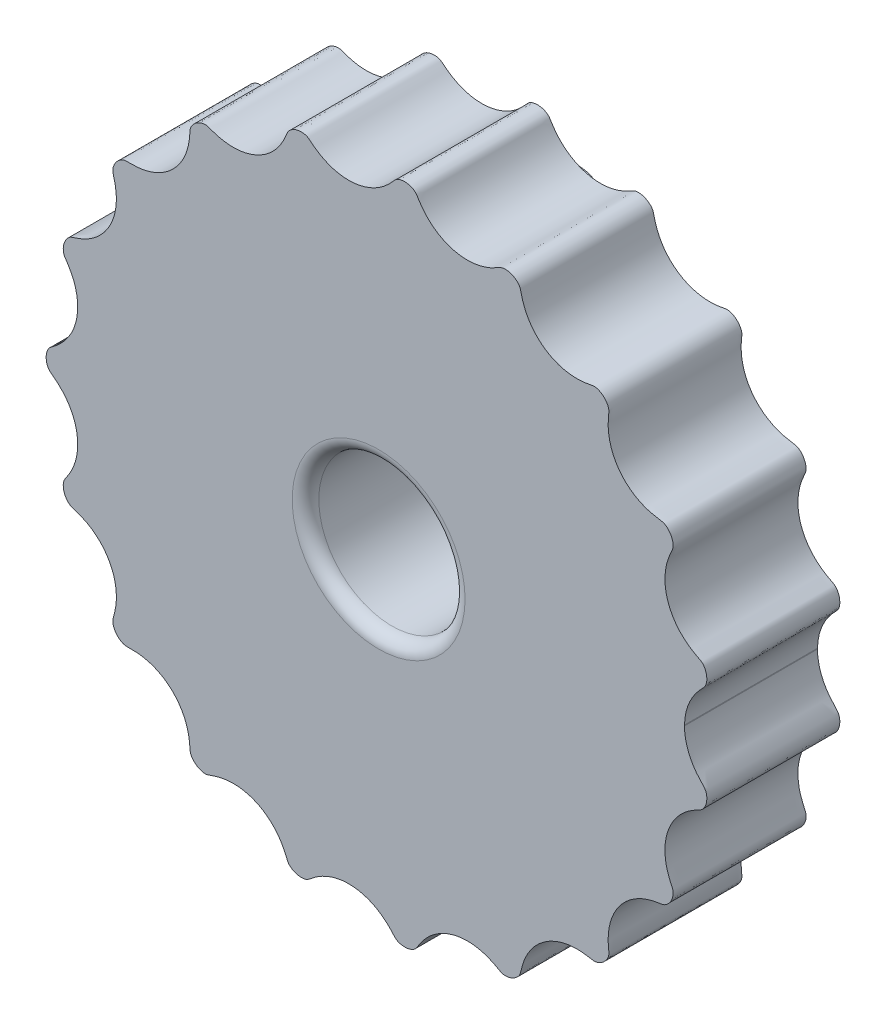
SolidWorks part; units mm, degrees
ref_plane "Ebene vorne" through (0, 0, 0) normal (0, 0, 1) x (1, 0, 0)
ref_plane "Ebene oben" through (0, 0, 0) normal (0, 1, 0) x (1, 0, 0)
ref_plane "Ebene rechts" through (0, 0, 0) normal (1, 0, 0) x (0, 0, -1)
sketch "Skizze1" plane through (0, 0, 0) normal (0, 0, 1) x (1, 0, 0)
  circle A0 centre (0, 0) radius 25
  dimension "D1" = 50
extrude "Aufsatz-Linear austragen1" add sketch "Skizze1" along normal blind 10 contours A0
sketch "Skizze3" plane through (0, 0, 10) normal (0, 0, 1) x (1, 0, 0)
  circle A0 centre (0, 25) radius 0.5
  circle A1 centre (0, 0) radius 25 construction
extrude "Schnitt-Linear austragen1" cut sketch "Skizze3" against normal up to next contours A0
pattern_circular "Kreismuster3" [suppressed] count 30 over 360 of bodies 102
sketch "Skizze9" plane through (0, 0, 10) normal (0, 0, 1) x (1, 0, 0)
  line L0 (23.0004, 0.0609) -> (23, 0)
  spline S0 degree 4 poles (21.8349, 10.4363) (21.7595, 10.2402) (21.6296, 9.8393) (21.51, 9.2154) (21.5169, 8.368) (21.6949, 7.529) (21.9996, 6.8362) (22.3616, 6.2918) (22.7278, 5.8789) (23.0126, 5.6175) (23.2743, 5.4145) (23.4929, 5.2661) (23.6607, 5.1622) (23.8217, 5.0701) (23.9556, 4.9977) (24.0711, 4.9376) (24.1728, 4.8842) (24.259, 4.8347) (24.3648, 4.7517) (24.4596, 4.6337) (24.5411, 4.4963) (24.6203, 4.3033) (24.6742, 4.0826) (24.6893, 3.8352) (24.654, 3.6047) (24.5939, 3.4337) (24.5231, 3.3149) (24.4482, 3.2274) (24.3391, 3.1139) (24.2149, 2.9815) (24.0838, 2.8346) (23.9185, 2.6346) (23.746, 2.4006) (23.5642, 2.1174) (23.3859, 1.7712) (23.2392, 1.419) (23.1381, 1.082) (23.0724, 0.8012) (23.0325, 0.5259) (23.0102, 0.3454) (22.9992, 0.0775) (22.999, -0.0665) (23.009, -0.3222) (23.0286, -0.4951) (23.0652, -0.7605) (23.1283, -1.0483) (23.2566, -1.484) (23.4559, -1.9318) (23.6809, -2.3132) (23.9099, -2.6224) (24.0743, -2.8241) (24.2067, -2.9723) (24.3336, -3.1084) (24.4467, -3.2256) (24.524, -3.3159) (24.583, -3.4156) (24.6246, -3.5208) (24.6638, -3.6686) (24.6852, -3.8609) (24.6735, -4.0869) (24.6205, -4.3068) (24.5464, -4.4848) (24.4695, -4.6144) (24.4037, -4.7024) (24.3311, -4.7784) (24.2516, -4.8395) (24.1377, -4.9039) (24.0001, -4.974) (23.846, -5.0565) (23.6352, -5.1762) (23.3933, -5.3292) (23.1212, -5.5276) (22.8316, -5.7799) (22.5655, -6.0569) (22.2617, -6.4361) (21.9548, -6.9332) (21.7249, -7.4811) (21.5829, -8.0653) (21.5273, -8.5636) (21.5216, -8.9708) (21.5541, -9.3694) (21.6218, -9.7561) (21.7087, -10.0818) (21.7995, -10.3483) (21.8842, -10.5632) (21.9558, -10.729) (22.0248, -10.8829) (22.0924, -11.0248) (22.1404, -11.1746) (22.1504, -11.3468) (22.1274, -11.5442) (22.061, -11.7619) (21.9505, -11.9788) (21.8083, -12.1674) (21.6614, -12.3022) (21.5247, -12.3914) (21.414, -12.4372) (21.3301, -12.4586) (21.2321, -12.4761) (21.1212, -12.4922) (20.9921, -12.5121) (20.8374, -12.539) (20.6763, -12.5709) (20.4655, -12.6198) (20.1205, -12.7175) (19.6539, -12.8972) (19.0899, -13.2109) (18.4957, -13.6939) (17.9798, -14.3033) (17.5818, -15.0184) (17.3599, -15.7125) (17.2758, -16.2728) (17.2579, -16.6757) (17.2603, -16.9123) (17.2683, -17.0871) (17.2802, -17.2498) (17.2921, -17.3816) (17.3037, -17.4944) (17.3123, -17.5952) (17.3148, -17.684) (17.3037, -17.7848) (17.2728, -17.8946) (17.2143, -18.0352) (17.1157, -18.1992) (16.9706, -18.3697) (16.7741, -18.5306) (16.5633, -18.6445) (16.3771, -18.7041) (16.228, -18.7183) (16.1024, -18.7064) (15.9827, -18.6847) (15.837, -18.6581) (15.664, -18.6292) (15.4825, -18.6042) (15.2505, -18.5802) (14.9676, -18.5655) (14.5429, -18.5729) (14.0693, -18.6361) (13.6043, -18.7559) (13.0666, -18.9667) (12.6278, -19.2052) (12.2149, -19.5036) (11.8389, -19.8586) (11.5583, -20.1838) (11.3157, -20.5303) (11.1115, -20.893) (10.9662, -21.2192) (10.865, -21.4994) (10.7941, -21.7329) (10.7511, -21.8937) (10.717, -22.0322) (10.6867, -22.159) (10.6596, -22.2741) (10.6135, -22.4098) (10.5273, -22.5357) (10.4274, -22.6442) (10.2911, -22.7583) (10.1265, -22.8625) (9.947, -22.94) (9.7581, -22.9885) (9.581, -23.009) (9.446, -23.0074) (9.3222, -22.9883) (9.215, -22.9494) (9.1367, -22.9105) (9.0374, -22.8556) (8.9163, -22.7867) (8.7704, -22.7082) (8.5994, -22.6214) (8.2969, -22.4821) (7.9364, -22.3488) (7.5146, -22.2402) (7.0313, -22.1759) (6.6328, -22.1607) (6.2298, -22.1836) (5.826, -22.2463) (5.4253, -22.3496) (5.032, -22.4941) (4.6565, -22.6767) (4.3023, -22.8948) (3.9755, -23.1429) (3.6777, -23.4168) (3.4441, -23.6748) (3.264, -23.904) (3.127, -24.0974) (3.026, -24.2496) (2.9434, -24.3794) (2.8771, -24.486) (2.8107, -24.5788) (2.7442, -24.6523) (2.6543, -24.7214) (2.5172, -24.8007) (2.3431, -24.8698) (2.129, -24.9172) (1.9104, -24.9257) (1.7254, -24.9049) (1.5597, -24.8634) (1.4272, -24.8123) (1.3018, -24.7374) (1.1919, -24.6254) (1.0929, -24.5126) (0.9862, -24.3949) (0.8714, -24.2728) (0.7167, -24.1173) (0.5166, -23.934) (0.1944, -23.6752) (-0.2816, -23.3734) (-0.8873, -23.1037) (-1.633, -22.9219) (-2.4119, -22.88) (-3.1838, -22.9833) (-3.829, -23.1953) (-4.2989, -23.431) (-4.6166, -23.6302) (-4.8236, -23.7746) (-4.9777, -23.8915) (-5.1193, -24.0037) (-5.2422, -24.1039) (-5.3368, -24.1704) (-5.4383, -24.2183) (-5.5428, -24.2496) (-5.6869, -24.2756) (-5.8715, -24.2822) (-6.0864, -24.2562) (-6.2931, -24.1927) (-6.4597, -24.1129) (-6.6006, -24.0204) (-6.7112, -23.9272) (-6.7966, -23.8241) (-6.8508, -23.7158) (-6.8984, -23.6058) (-6.9474, -23.4882) (-7.0086, -23.3469) (-7.0843, -23.183) (-7.1853, -22.982) (-7.3178, -22.7471) (-7.4915, -22.481) (-7.7159, -22.1922) (-7.9683, -21.919) (-8.2484, -21.6651) (-8.561, -21.4293) (-9, -21.1594) (-9.4852, -20.944) (-10.0058, -20.7949) (-10.5401, -20.7187) (-10.9664, -20.7017) (-11.386, -20.7263) (-11.7441, -20.7819) (-12.0407, -20.8508) (-12.2801, -20.9199) (-12.4645, -20.9804) (-12.619, -21.0347) (-12.7443, -21.0813) (-12.8432, -21.1127) (-12.9148, -21.1293) (-13.0155, -21.1409) (-13.1607, -21.1341) (-13.3458, -21.0947) (-13.5626, -21.0052) (-13.7727, -20.87) (-13.9463, -20.7079) (-14.067, -20.5439) (-14.1433, -20.3907) (-14.1772, -20.2506) (-14.1869, -20.1194) (-14.1984, -19.9464) (-14.2135, -19.7574) (-14.2357, -19.56) (-14.2744, -19.3096) (-14.3484, -18.9507) (-14.4988, -18.4602) (-14.7821, -17.8614) (-15.2347, -17.2299) (-15.8123, -16.6797) (-16.4915, -16.2457) (-17.1512, -15.9856) (-17.6884, -15.8653) (-18.0779, -15.8187) (-18.3444, -15.8008) (-18.5515, -15.7964) (-18.7472, -15.7971) (-18.9192, -15.8013) (-19.043, -15.798) (-19.1585, -15.7742) (-19.2639, -15.7342) (-19.3981, -15.6643) (-19.5524, -15.5524) (-19.7098, -15.3942) (-19.8355, -15.2104) (-19.9175, -15.0392) (-19.9694, -14.8748) (-19.9942, -14.7409) (-19.9941, -14.6091) (-19.9622, -14.4594) (-19.9209, -14.3132) (-19.8775, -14.147) (-19.8227, -13.9154) (-19.7703, -13.6388) (-19.7298, -13.3095) (-19.7155, -12.9316) (-19.7343, -12.5536) (-19.7865, -12.1771) (-19.8725, -11.8051) (-20.0235, -11.3478) (-20.2355, -10.9007) (-20.5061, -10.4779) (-20.8313, -10.0898) (-21.1296, -9.7984) (-21.4493, -9.5419) (-21.7859, -9.3207) (-22.0908, -9.1576) (-22.3541, -9.0395) (-22.5745, -8.9534) (-22.7489, -8.8919) (-22.9125, -8.8369) (-23.0664, -8.7897) (-23.2127, -8.7239) (-23.3488, -8.6133) (-23.48, -8.461) (-23.5959, -8.2631) (-23.6806, -8.0335) (-23.7223, -7.802) (-23.7216, -7.6015) (-23.6936, -7.4372) (-23.6459, -7.3113) (-23.587, -7.2131) (-23.5046, -7.0919) (-23.4135, -6.9559) (-23.317, -6.8055) (-23.1954, -6.601) (-23.0687, -6.3633) (-22.9383, -6.0757) (-22.7839, -5.6451) (-22.656, -5.1008) (-22.5992, -4.4221) (-22.6826, -3.6209) (-22.9272, -2.8308) (-23.2818, -2.1836) (-23.6363, -1.7308) (-23.9221, -1.4366) (-24.1011, -1.2722) (-24.239, -1.1546) (-24.372, -1.0482) (-24.4823, -0.963) (-24.578, -0.8915) (-24.662, -0.827) (-24.7323, -0.7672) (-24.8009, -0.6902) (-24.8613, -0.5932) (-24.925, -0.4573) (-24.9789, -0.2784) (-25.008, -0.0615) (-24.998, 0.1569) (-24.9616, 0.3399) (-24.9066, 0.5001) (-24.8504, 0.6156) (-24.7832, 0.7138) (-24.7061, 0.7903) (-24.6412, 0.8433) (-24.5549, 0.909) (-24.4487, 0.9887) (-24.3242, 1.0855) (-24.1833, 1.2011) (-24.0105, 1.3531) (-23.8111, 1.5469) (-23.5946, 1.788) (-23.3715, 2.0829) (-23.1734, 2.3976) (-23.0026, 2.7303) (-22.8251, 3.1685) (-22.6969, 3.6432) (-22.6277, 4.1442) (-22.6242, 4.6617) (-22.6664, 5.0951) (-22.7519, 5.5174) (-22.8777, 5.9244) (-23.0193, 6.2625) (-23.1587, 6.5356) (-23.2844, 6.7524) (-23.3883, 6.9169) (-23.4888, 7.0702) (-23.5875, 7.2108) (-23.6712, 7.3568) (-23.7142, 7.5309) (-23.7261, 7.7309) (-23.6995, 7.9535) (-23.6303, 8.1831) (-23.5263, 8.3908) (-23.4082, 8.549) (-23.2912, 8.6625) (-23.187, 8.7339) (-23.0968, 8.7758) (-22.9816, 8.8159) (-22.8484, 8.8583) (-22.6971, 8.9097) (-22.4871, 8.9859) (-22.2435, 9.0865) (-21.9662, 9.221) (-21.6596, 9.4005) (-21.366, 9.6063) (-21.0151, 9.8992) (-20.6164, 10.3191) (-20.2771, 10.8105) (-20.0144, 11.3636) (-19.8542, 11.8663) (-19.7673, 12.2789) (-19.7222, 12.6923) (-19.7169, 13.1024) (-19.7451, 13.4552) (-19.7902, 13.7494) (-19.8394, 13.9878) (-19.8839, 14.1718) (-19.9244, 14.3263) (-19.9596, 14.452) (-19.9815, 14.5509) (-19.9911, 14.6219) (-19.9935, 14.7217) (-19.9742, 14.8643) (-19.9195, 15.0445) (-19.8125, 15.2522) (-19.6794, 15.4254) (-19.5437, 15.5557) (-19.4017, 15.6607) (-19.2787, 15.7293) (-19.1504, 15.7794) (-19.0246, 15.7985) (-18.927, 15.8005) (-18.8133, 15.7991) (-18.6836, 15.7969) (-18.532, 15.7969) (-18.3106, 15.8023) (-18.0413, 15.8209) (-17.7248, 15.8628) (-17.3647, 15.941) (-16.9178, 16.0786) (-16.3974, 16.3085) (-15.8239, 16.6734) (-15.2485, 17.213) (-14.783, 17.8542) (-14.4878, 18.4827) (-14.3351, 18.9986) (-14.2627, 19.3751) (-14.2269, 19.6306) (-14.2075, 19.8274) (-14.1936, 20.0116) (-14.184, 20.1733) (-14.1697, 20.2905) (-14.1362, 20.4005) (-14.0873, 20.5015) (-14.0059, 20.6294) (-13.8804, 20.7742) (-13.7077, 20.9182) (-13.5127, 21.0276) (-13.335, 21.0939) (-13.1647, 21.1311) (-13.0232, 21.1444) (-12.8817, 21.1276) (-12.7469, 21.0817) (-12.6315, 21.0398) (-12.5001, 20.993) (-12.3519, 20.9431) (-12.1413, 20.8781) (-11.8655, 20.8075) (-11.5389, 20.7468) (-11.1616, 20.7097) (-10.7833, 20.7056) (-10.3038, 20.7432) (-9.7354, 20.8584) (-9.1818, 21.0633) (-8.6608, 21.3563) (-8.2599, 21.6542) (-7.9581, 21.9276) (-7.6875, 22.2243) (-7.4782, 22.5013) (-7.318, 22.7492) (-7.2006, 22.9556) (-7.1162, 23.1178) (-7.0401, 23.2775) (-6.9792, 23.4143) (-6.929, 23.5322) (-6.8829, 23.6417) (-6.8396, 23.7425) (-6.7732, 23.8583) (-6.6528, 23.9827) (-6.4911, 24.0996) (-6.2848, 24.1982) (-6.0489, 24.2635) (-5.8125, 24.2858) (-5.6133, 24.2679) (-5.4554, 24.2266) (-5.3475, 24.1752) (-5.2756, 24.1275) (-5.1963, 24.0667) (-5.1084, 23.9955) (-5.0052, 23.9133) (-4.8796, 23.817) (-4.7458, 23.7196) (-4.5657, 23.5973) (-4.2579, 23.4095) (-3.8065, 23.1883) (-3.1897, 22.9875) (-2.4297, 22.8812) (-1.6328, 22.9188) (-0.8411, 23.1135) (-0.1854, 23.421) (0.2799, 23.7378) (0.5861, 23.9964) (0.7572, 24.1576) (0.8795, 24.2813) (0.9904, 24.3996) (1.0788, 24.4971) (1.1534, 24.5815) (1.2215, 24.6556) (1.2849, 24.7171) (1.366, 24.7765) (1.4665, 24.8274) (1.6073, 24.879) (1.7912, 24.9173) (2.0109, 24.9275) (2.2284, 24.8982) (2.4076, 24.8457) (2.5635, 24.7759) (2.6787, 24.7064) (2.7776, 24.6216) (2.853, 24.522) (2.9089, 24.4353) (2.9741, 24.3312) (3.0513, 24.2111) (3.1673, 24.0378) (3.3314, 23.8136) (3.5412, 23.5623) (3.803, 23.2967) (4.0867, 23.0548) (4.3911, 22.8375) (4.7145, 22.6472) (5.1434, 22.4443) (5.6099, 22.2897) (6.1032, 22.1928) (6.6136, 22.1597) (7.04, 22.1755) (7.456, 22.233) (7.8578, 22.329) (8.1935, 22.443) (8.4659, 22.558) (8.6842, 22.6634) (8.8514, 22.7516) (9.0063, 22.8365) (9.1484, 22.9196) (9.3008, 22.9869) (9.4518, 23.0083) (9.5997, 23.0081) (9.7768, 22.9846) (9.9657, 22.9334) (10.1449, 22.8528) (10.3091, 22.7455) (10.4441, 22.6278) (10.5341, 22.5264) (10.6032, 22.4212) (10.6459, 22.3149) (10.6698, 22.2304) (10.6965, 22.1196) (10.7284, 21.9833) (10.7696, 21.8219) (10.8224, 21.6365) (10.926, 21.3181) (11.074, 20.9612) (11.2824, 20.576) (11.5658, 20.1761) (11.8273, 19.8724) (12.1194, 19.5924) (12.4404, 19.3397) (12.8767, 19.0608) (13.3474, 18.8414) (13.8414, 18.6865) (14.3466, 18.5977) (14.6978, 18.5693) (14.9983, 18.5678) (15.2424, 18.5806) (15.4319, 18.5983) (15.6163, 18.622) (15.7956, 18.651) (15.9629, 18.6804) (16.1188, 18.7114) (16.2634, 18.7186) (16.3919, 18.6957) (16.5434, 18.6484) (16.7128, 18.5663) (16.8932, 18.44) (17.0477, 18.2836) (17.1576, 18.1324) (17.2387, 17.9815) (17.2904, 17.8485) (17.3189, 17.7045) (17.3093, 17.5471) (17.2934, 17.3968) (17.2791, 17.2377) (17.2672, 17.07) (17.2581, 16.8499) (17.2594, 16.5774) (17.2886, 16.1632) (17.3914, 15.6061) (17.6071, 14.9758) (17.9828, 14.3047) (18.4824, 13.7066) (19.0811, 13.2137) (19.6713, 12.887) (20.16, 12.7034) (20.5195, 12.6059) (20.7644, 12.5521) (20.9536, 12.5182) (21.1309, 12.4903) (21.2868, 12.4679) (21.399, 12.4432) (21.5025, 12.4008) (21.5963, 12.345) (21.7134, 12.2561) (21.8437, 12.1238) (21.9702, 11.9469) (22.0634, 11.7504) (22.117, 11.5726) (22.1436, 11.4054) (22.149, 11.2598) (22.129, 11.1267) (22.0845, 11.0132) (22.035, 10.903) (21.9816, 10.7867) (21.919, 10.6454) (21.8499, 10.4782) (21.7706, 10.2666) (21.6878, 10.0086) (21.6103, 9.6986) (21.5509, 9.3355) (21.5224, 8.9626) (21.5272, 8.5827) (21.5787, 8.0866) (21.6972, 7.5846) (21.8865, 7.0905) (22.1457, 6.6199) (22.3909, 6.2662) (22.6666, 5.9438) (22.9679, 5.6541) (23.2503, 5.43) (23.5008, 5.2597) (23.7129, 5.1314) (23.8814, 5.0373) (24.0251, 4.9609) (24.1437, 4.9005) (24.2332, 4.8492) (24.2935, 4.8079) (24.37, 4.7415) (24.4633, 4.6297) (24.5599, 4.466) (24.6407, 4.2447) (24.683, 3.9972) (24.6804, 3.7586) (24.6403, 3.558) (24.5776, 3.3979) (24.4956, 3.2786) (24.4048, 3.1827) (24.2851, 3.0565) (24.1558, 2.9165) (24.0253, 2.7659) (23.8669, 2.5657) (23.6527, 2.2673) (23.442, 1.9019) (23.2546, 1.4742) (23.132, 1.0608) (23.0706, 0.7861) (23.0335, 0.5349) (23.0132, 0.3678) (23.0003, 0.1223) (22.9986, -0.0189) (23.0056, -0.2852) (23.0253, -0.4661) (23.0615, -0.7427) (23.1239, -1.029) (23.2494, -1.4644) (23.4447, -1.9094) (23.6681, -2.2941) (23.8991, -2.6086) (24.0657, -2.8141) (24.1984, -2.9632) (24.3246, -3.0987) (24.4356, -3.2143) (24.5132, -3.3018) (24.5877, -3.4196) (24.6374, -3.5547) (24.6701, -3.7073) (24.6838, -3.9154) (24.6644, -4.1417) (24.6, -4.381) (24.4916, -4.5912) (24.3759, -4.7394) (24.2736, -4.8247) (24.1898, -4.8749) (24.0901, -4.9279) (23.9765, -4.9865) (23.845, -5.0574) (23.6862, -5.1471) (23.5208, -5.2483) (23.3047, -5.3926) (23.0455, -5.59) (22.7627, -5.8442) (22.3976, -6.2458) (22.0314, -6.7792) (21.7172, -7.4627) (21.5252, -8.2962) (21.504, -9.1452) (21.6139, -9.7724) (21.7382, -10.176) (21.8113, -10.3736) knots 0 0 0 0 0 0.004237 0.008483 0.012729 0.016973 0.021413 0.023634 0.025855 0.02808 0.029193 0.030306 0.031182 0.032058 0.032934 0.033372 0.03381 0.034372 0.034934 0.036073 0.036831 0.037589 0.039124 0.04064 0.041779 0.042264 0.042749 0.043421 0.044093 0.045438 0.046411 0.047385 0.049332 0.051278 0.053223 0.055168 0.057112 0.0582 0.059287 0.060374 0.061462 0.062481 0.063501 0.064521 0.06554 0.067576 0.069612 0.073551 0.075471 0.07643 0.07739 0.078785 0.079482 0.08018 0.080676 0.081172 0.081811 0.082451 0.083753 0.085056 0.086348 0.086986 0.087623 0.08809 0.088558 0.089098 0.089639 0.090721 0.091672 0.092623 0.094526 0.09649 0.098454 0.100357 0.102259 0.106274 0.110193 0.112266 0.114339 0.116366 0.118392 0.120318 0.122244 0.123155 0.124065 0.124975 0.125886 0.126558 0.12723 0.128129 0.12933 0.130553 0.131784 0.13302 0.134061 0.134556 0.135052 0.135429 0.135805 0.136559 0.137312 0.138066 0.138968 0.13987 0.141675 0.145292 0.149024 0.152819 0.157032 0.161293 0.165414 0.167417 0.168419 0.16942 0.170182 0.170945 0.171707 0.172088 0.17247 0.172983 0.173496 0.174127 0.174758 0.176047 0.177335 0.178622 0.179842 0.180858 0.181239 0.181621 0.182383 0.183306 0.18423 0.185154 0.186077 0.188008 0.189939 0.193707 0.195683 0.19766 0.201566 0.203743 0.205919 0.208066 0.210213 0.212256 0.214298 0.215257 0.216216 0.217175 0.217654 0.218133 0.218845 0.219557 0.220527 0.221173 0.221818 0.22313 0.224442 0.22509 0.225738 0.226717 0.227156 0.227596 0.228035 0.228475 0.229441 0.230408 0.231375 0.232341 0.236155 0.238143 0.24013 0.242157 0.244184 0.24627 0.248355 0.250487 0.252618 0.254674 0.25673 0.258747 0.260763 0.261683 0.262604 0.263524 0.264444 0.264789 0.265133 0.265821 0.26644 0.267059 0.26832 0.269582 0.270836 0.271447 0.272058 0.273021 0.273691 0.274361 0.275205 0.27605 0.276894 0.277739 0.279628 0.281518 0.285219 0.28907 0.292926 0.296908 0.300855 0.304679 0.306545 0.307478 0.308411 0.309767 0.310445 0.311123 0.311607 0.31209 0.312702 0.313313 0.314555 0.3158 0.31704 0.317653 0.318265 0.319194 0.319946 0.320323 0.320699 0.321608 0.322518 0.323427 0.324337 0.326144 0.327952 0.329828 0.331704 0.333634 0.335564 0.337712 0.342077 0.344294 0.346435 0.348576 0.350665 0.352755 0.353733 0.35471 0.355688 0.356666 0.357036 0.357406 0.357777 0.358147 0.359078 0.360318 0.361577 0.362842 0.364095 0.365072 0.365667 0.366263 0.366989 0.367716 0.369169 0.370082 0.370996 0.372823 0.376553 0.380398 0.384283 0.388402 0.39254 0.396544 0.398494 0.399468 0.400443 0.401928 0.402671 0.403414 0.403914 0.404414 0.405044 0.405674 0.406958 0.408242 0.409517 0.410142 0.410767 0.411715 0.412247 0.41278 0.413844 0.414778 0.415711 0.417578 0.419518 0.421458 0.423328 0.425198 0.427172 0.429146 0.433023 0.435141 0.437259 0.439338 0.441417 0.443393 0.445369 0.446301 0.447232 0.448164 0.449096 0.449784 0.450473 0.451382 0.452594 0.453825 0.455064 0.456299 0.457303 0.457852 0.458401 0.459003 0.459604 0.460806 0.461705 0.462604 0.464401 0.466234 0.468066 0.471816 0.475642 0.479892 0.484207 0.488376 0.490424 0.491448 0.492472 0.493275 0.494078 0.494881 0.495283 0.495684 0.496212 0.496739 0.497357 0.497975 0.499232 0.500491 0.501743 0.502362 0.50298 0.503902 0.504323 0.504745 0.505167 0.505588 0.506507 0.507426 0.508345 0.509264 0.511146 0.513029 0.51487 0.51671 0.518635 0.520559 0.52439 0.526593 0.528795 0.530975 0.533155 0.535264 0.537372 0.538353 0.539334 0.540315 0.541296 0.542048 0.5428 0.543686 0.54487 0.546076 0.547289 0.548505 0.549524 0.55004 0.550557 0.551041 0.551525 0.552494 0.553378 0.554262 0.556029 0.557808 0.559586 0.561418 0.563249 0.567013 0.571226 0.573386 0.575547 0.57763 0.579713 0.581758 0.583803 0.584757 0.585711 0.586665 0.587619 0.587981 0.588342 0.588703 0.589064 0.589991 0.591226 0.592482 0.593745 0.594375 0.595005 0.596035 0.596581 0.597126 0.597563 0.597999 0.598872 0.599744 0.600617 0.602465 0.604312 0.606175 0.608037 0.611883 0.615748 0.619804 0.623847 0.62776 0.629667 0.63062 0.631574 0.63296 0.633653 0.634347 0.63484 0.635333 0.635965 0.636598 0.63789 0.639181 0.640471 0.641084 0.641696 0.642695 0.643315 0.643934 0.644554 0.645174 0.64613 0.647085 0.648997 0.65091 0.652822 0.654719 0.656616 0.660595 0.664476 0.666551 0.668626 0.67065 0.672674 0.674636 0.675617 0.676598 0.67746 0.678322 0.679184 0.679615 0.680046 0.680718 0.68139 0.682294 0.683501 0.68473 0.685967 0.68721 0.688256 0.688745 0.689234 0.689614 0.689994 0.690755 0.691516 0.692276 0.693184 0.694091 0.695906 0.699541 0.703294 0.707104 0.711296 0.715529 0.719623 0.721614 0.722609 0.723605 0.724363 0.72512 0.725878 0.726257 0.726636 0.727147 0.727657 0.728278 0.728898 0.730163 0.731429 0.732687 0.7333 0.733914 0.734868 0.735387 0.735906 0.736425 0.736945 0.737866 0.738787 0.740628 0.742544 0.74446 0.746298 0.748136 0.750076 0.752015 0.75585 0.758014 0.760177 0.762308 0.764439 0.766466 0.768494 0.769446 0.770399 0.771352 0.772304 0.773011 0.773717 0.774692 0.775341 0.77599 0.777308 0.778627 0.779278 0.77993 0.780912 0.781353 0.781795 0.782237 0.782678 0.78365 0.784622 0.785593 0.786565 0.790399 0.792398 0.794396 0.796432 0.798468 0.800544 0.802619 0.806855 0.808898 0.810941 0.812947 0.81395 0.814953 0.815868 0.816783 0.817698 0.818613 0.819297 0.819981 0.820603 0.821225 0.822492 0.82376 0.825019 0.825633 0.826247 0.827208 0.827886 0.828563 0.829411 0.830258 0.831106 0.831953 0.833852 0.83575 0.83947 0.843342 0.847212 0.851172 0.85509 0.858888 0.860742 0.861669 0.862595 0.863943 0.864616 0.86529 0.86577 0.866251 0.866866 0.86748 0.868728 0.86998 0.871226 0.871843 0.872459 0.87339 0.87415 0.87453 0.874909 0.875821 0.876733 0.877645 0.878557 0.880376 0.882194 0.884081 0.885968 0.887906 0.889845 0.894123 0.896327 0.898531 0.900659 0.902786 0.904866 0.906945 0.907918 0.90889 0.909862 0.910835 0.911203 0.911571 0.911939 0.912307 0.913243 0.914489 0.915755 0.917025 0.918283 0.919266 0.919863 0.920461 0.92119 0.921919 0.923377 0.924296 0.925215 0.927054 0.930802 0.932735 0.934668 0.935643 0.936618 0.937593 0.938568 0.939657 0.940745 0.941834 0.942922 0.944896 0.946869 0.950817 0.952789 0.953776 0.954762 0.956135 0.956821 0.957507 0.957996 0.958485 0.959623 0.960381 0.961139 0.962673 0.964189 0.965328 0.965881 0.966433 0.966863 0.967294 0.968154 0.969015 0.969875 0.970969 0.972064 0.974253 0.976438 0.978623 0.98299 0.987244 0.991499 0.995751 1 1 1 1 1 construction
  spline S1 degree 4 poles (23, 0) (23, -0.0443) (23.0016, -0.1335) (23.009, -0.3222) (23.0286, -0.4951) (23.0652, -0.7605) (23.1283, -1.0483) (23.2566, -1.484) (23.4559, -1.9318) (23.6809, -2.3132) (23.9099, -2.6224) (24.0743, -2.8241) (24.2067, -2.9723) (24.3336, -3.1084) (24.4467, -3.2256) (24.524, -3.3159) (24.583, -3.4156) (24.6246, -3.5208) (24.6638, -3.6686) (24.6852, -3.8609) (24.6735, -4.0869) (24.6205, -4.3068) (24.5464, -4.4848) (24.4695, -4.6144) (24.4037, -4.7024) (24.3311, -4.7784) (24.2516, -4.8395) (24.1377, -4.9039) (24.0001, -4.974) (23.846, -5.0565) (23.6352, -5.1762) (23.3933, -5.3292) (23.1212, -5.5276) (22.8316, -5.7799) (22.5655, -6.0569) (22.2617, -6.4361) (21.9548, -6.9332) (21.7249, -7.4811) (21.5829, -8.0653) (21.5273, -8.5636) (21.5216, -8.9708) (21.5541, -9.3694) (21.6218, -9.7561) (21.7087, -10.0818) (21.7995, -10.3483) (21.8842, -10.5632) (21.9558, -10.729) (22.0248, -10.8829) (22.0924, -11.0248) (22.1404, -11.1746) (22.1504, -11.3468) (22.1274, -11.5442) (22.061, -11.7619) (21.9505, -11.9788) (21.8083, -12.1674) (21.6614, -12.3022) (21.5247, -12.3914) (21.414, -12.4372) (21.3301, -12.4586) (21.2321, -12.4761) (21.1212, -12.4922) (20.9921, -12.5121) (20.8374, -12.539) (20.6763, -12.5709) (20.4655, -12.6198) (20.1205, -12.7175) (19.6539, -12.8972) (19.0899, -13.2109) (18.4957, -13.6939) (17.9798, -14.3033) (17.5818, -15.0184) (17.3599, -15.7125) (17.2758, -16.2728) (17.2579, -16.6757) (17.2603, -16.9123) (17.2683, -17.0871) (17.2802, -17.2498) (17.2921, -17.3816) (17.3037, -17.4944) (17.3123, -17.5952) (17.3148, -17.684) (17.3037, -17.7848) (17.2728, -17.8946) (17.2143, -18.0352) (17.1157, -18.1992) (16.9706, -18.3697) (16.7741, -18.5306) (16.5633, -18.6445) (16.3771, -18.7041) (16.228, -18.7183) (16.1024, -18.7064) (15.9827, -18.6847) (15.837, -18.6581) (15.664, -18.6292) (15.4825, -18.6042) (15.2505, -18.5802) (14.9676, -18.5655) (14.5429, -18.5729) (14.0693, -18.6361) (13.6043, -18.7559) (13.0666, -18.9667) (12.6278, -19.2052) (12.2149, -19.5036) (11.8389, -19.8586) (11.5583, -20.1838) (11.3157, -20.5303) (11.1115, -20.893) (10.9662, -21.2192) (10.865, -21.4994) (10.7941, -21.7329) (10.7511, -21.8937) (10.717, -22.0322) (10.6867, -22.159) (10.6596, -22.2741) (10.6135, -22.4098) (10.5273, -22.5357) (10.4274, -22.6442) (10.2911, -22.7583) (10.1265, -22.8625) (9.947, -22.94) (9.7581, -22.9885) (9.581, -23.009) (9.446, -23.0074) (9.3222, -22.9883) (9.215, -22.9494) (9.1367, -22.9105) (9.0374, -22.8556) (8.9163, -22.7867) (8.7704, -22.7082) (8.5994, -22.6214) (8.2969, -22.4821) (7.9364, -22.3488) (7.5146, -22.2402) (7.0313, -22.1759) (6.6328, -22.1607) (6.2298, -22.1836) (5.826, -22.2463) (5.4253, -22.3496) (5.032, -22.4941) (4.6565, -22.6767) (4.3023, -22.8948) (3.9755, -23.1429) (3.6777, -23.4168) (3.4441, -23.6748) (3.264, -23.904) (3.127, -24.0974) (3.026, -24.2496) (2.9434, -24.3794) (2.8771, -24.486) (2.8107, -24.5788) (2.7442, -24.6523) (2.6543, -24.7214) (2.5172, -24.8007) (2.3431, -24.8698) (2.129, -24.9172) (1.9104, -24.9257) (1.7254, -24.9049) (1.5597, -24.8634) (1.4272, -24.8123) (1.3018, -24.7374) (1.1919, -24.6254) (1.0929, -24.5126) (0.9862, -24.3949) (0.8714, -24.2728) (0.7167, -24.1173) (0.5166, -23.934) (0.1944, -23.6752) (-0.2816, -23.3734) (-0.8873, -23.1037) (-1.633, -22.9219) (-2.4119, -22.88) (-3.1838, -22.9833) (-3.829, -23.1953) (-4.2989, -23.431) (-4.6166, -23.6302) (-4.8236, -23.7746) (-4.9777, -23.8915) (-5.1193, -24.0037) (-5.2422, -24.1039) (-5.3368, -24.1704) (-5.4383, -24.2183) (-5.5428, -24.2496) (-5.6869, -24.2756) (-5.8715, -24.2822) (-6.0864, -24.2562) (-6.2931, -24.1927) (-6.4597, -24.1129) (-6.6006, -24.0204) (-6.7112, -23.9272) (-6.7966, -23.8241) (-6.8508, -23.7158) (-6.8984, -23.6058) (-6.9474, -23.4882) (-7.0086, -23.3469) (-7.0843, -23.183) (-7.1853, -22.982) (-7.3178, -22.7471) (-7.4915, -22.481) (-7.7159, -22.1922) (-7.9683, -21.919) (-8.2484, -21.6651) (-8.561, -21.4293) (-9, -21.1594) (-9.4852, -20.944) (-10.0058, -20.7949) (-10.5401, -20.7187) (-10.9664, -20.7017) (-11.386, -20.7263) (-11.7441, -20.7819) (-12.0407, -20.8508) (-12.2801, -20.9199) (-12.4645, -20.9804) (-12.619, -21.0347) (-12.7443, -21.0813) (-12.8432, -21.1127) (-12.9148, -21.1293) (-13.0155, -21.1409) (-13.1607, -21.1341) (-13.3458, -21.0947) (-13.5626, -21.0052) (-13.7727, -20.87) (-13.9463, -20.7079) (-14.067, -20.5439) (-14.1433, -20.3907) (-14.1772, -20.2506) (-14.1869, -20.1194) (-14.1984, -19.9464) (-14.2135, -19.7574) (-14.2357, -19.56) (-14.2744, -19.3096) (-14.3484, -18.9507) (-14.4988, -18.4602) (-14.7821, -17.8614) (-15.2347, -17.2299) (-15.8123, -16.6797) (-16.4915, -16.2457) (-17.1512, -15.9856) (-17.6884, -15.8653) (-18.0779, -15.8187) (-18.3444, -15.8008) (-18.5515, -15.7964) (-18.7472, -15.7971) (-18.9192, -15.8013) (-19.043, -15.798) (-19.1585, -15.7742) (-19.2639, -15.7342) (-19.3981, -15.6643) (-19.5524, -15.5524) (-19.7098, -15.3942) (-19.8355, -15.2104) (-19.9175, -15.0392) (-19.9694, -14.8748) (-19.9942, -14.7409) (-19.9941, -14.6091) (-19.9622, -14.4594) (-19.9209, -14.3132) (-19.8775, -14.147) (-19.8227, -13.9154) (-19.7703, -13.6388) (-19.7298, -13.3095) (-19.7155, -12.9316) (-19.7343, -12.5536) (-19.7865, -12.1771) (-19.8725, -11.8051) (-20.0235, -11.3478) (-20.2355, -10.9007) (-20.5061, -10.4779) (-20.8313, -10.0898) (-21.1296, -9.7984) (-21.4493, -9.5419) (-21.7859, -9.3207) (-22.0908, -9.1576) (-22.3541, -9.0395) (-22.5745, -8.9534) (-22.7489, -8.8919) (-22.9125, -8.8369) (-23.0664, -8.7897) (-23.2127, -8.7239) (-23.3488, -8.6133) (-23.48, -8.461) (-23.5959, -8.2631) (-23.6806, -8.0335) (-23.7223, -7.802) (-23.7216, -7.6015) (-23.6936, -7.4372) (-23.6459, -7.3113) (-23.587, -7.2131) (-23.5046, -7.0919) (-23.4135, -6.9559) (-23.317, -6.8055) (-23.1954, -6.601) (-23.0687, -6.3633) (-22.9383, -6.0757) (-22.7839, -5.6451) (-22.656, -5.1008) (-22.5992, -4.4221) (-22.6826, -3.6209) (-22.9272, -2.8308) (-23.2818, -2.1836) (-23.6363, -1.7308) (-23.9221, -1.4366) (-24.1011, -1.2722) (-24.239, -1.1546) (-24.372, -1.0482) (-24.4823, -0.963) (-24.578, -0.8915) (-24.662, -0.827) (-24.7323, -0.7672) (-24.8009, -0.6902) (-24.8613, -0.5932) (-24.925, -0.4573) (-24.9789, -0.2784) (-25.008, -0.0615) (-24.998, 0.1569) (-24.9616, 0.3399) (-24.9066, 0.5001) (-24.8504, 0.6156) (-24.7832, 0.7138) (-24.7061, 0.7903) (-24.6412, 0.8433) (-24.5549, 0.909) (-24.4487, 0.9887) (-24.3242, 1.0855) (-24.1833, 1.2011) (-24.0105, 1.3531) (-23.8111, 1.5469) (-23.5946, 1.788) (-23.3715, 2.0829) (-23.1734, 2.3976) (-23.0026, 2.7303) (-22.8251, 3.1685) (-22.6969, 3.6432) (-22.6277, 4.1442) (-22.6242, 4.6617) (-22.6664, 5.0951) (-22.7519, 5.5174) (-22.8777, 5.9244) (-23.0193, 6.2625) (-23.1587, 6.5356) (-23.2844, 6.7524) (-23.3883, 6.9169) (-23.4888, 7.0702) (-23.5875, 7.2108) (-23.6712, 7.3568) (-23.7142, 7.5309) (-23.7261, 7.7309) (-23.6995, 7.9535) (-23.6303, 8.1831) (-23.5263, 8.3908) (-23.4082, 8.549) (-23.2912, 8.6625) (-23.187, 8.7339) (-23.0968, 8.7758) (-22.9816, 8.8159) (-22.8484, 8.8583) (-22.6971, 8.9097) (-22.4871, 8.9859) (-22.2435, 9.0865) (-21.9662, 9.221) (-21.6596, 9.4005) (-21.366, 9.6063) (-21.0151, 9.8992) (-20.6164, 10.3191) (-20.2771, 10.8105) (-20.0144, 11.3636) (-19.8542, 11.8663) (-19.7673, 12.2789) (-19.7222, 12.6923) (-19.7169, 13.1024) (-19.7451, 13.4552) (-19.7902, 13.7494) (-19.8394, 13.9878) (-19.8839, 14.1718) (-19.9244, 14.3263) (-19.9596, 14.452) (-19.9815, 14.5509) (-19.9911, 14.6219) (-19.9935, 14.7217) (-19.9742, 14.8643) (-19.9195, 15.0445) (-19.8125, 15.2522) (-19.6794, 15.4254) (-19.5437, 15.5557) (-19.4017, 15.6607) (-19.2787, 15.7293) (-19.1504, 15.7794) (-19.0246, 15.7985) (-18.927, 15.8005) (-18.8133, 15.7991) (-18.6836, 15.7969) (-18.532, 15.7969) (-18.3106, 15.8023) (-18.0413, 15.8209) (-17.7248, 15.8628) (-17.3647, 15.941) (-16.9178, 16.0786) (-16.3974, 16.3085) (-15.8239, 16.6734) (-15.2485, 17.213) (-14.783, 17.8542) (-14.4878, 18.4827) (-14.3351, 18.9986) (-14.2627, 19.3751) (-14.2269, 19.6306) (-14.2075, 19.8274) (-14.1936, 20.0116) (-14.184, 20.1733) (-14.1697, 20.2905) (-14.1362, 20.4005) (-14.0873, 20.5015) (-14.0059, 20.6294) (-13.8804, 20.7742) (-13.7077, 20.9182) (-13.5127, 21.0276) (-13.335, 21.0939) (-13.1647, 21.1311) (-13.0232, 21.1444) (-12.8817, 21.1276) (-12.7469, 21.0817) (-12.6315, 21.0398) (-12.5001, 20.993) (-12.3519, 20.9431) (-12.1413, 20.8781) (-11.8655, 20.8075) (-11.5389, 20.7468) (-11.1616, 20.7097) (-10.7833, 20.7056) (-10.3038, 20.7432) (-9.7354, 20.8584) (-9.1818, 21.0633) (-8.6608, 21.3563) (-8.2599, 21.6542) (-7.9581, 21.9276) (-7.6875, 22.2243) (-7.4782, 22.5013) (-7.318, 22.7492) (-7.2006, 22.9556) (-7.1162, 23.1178) (-7.0401, 23.2775) (-6.9792, 23.4143) (-6.929, 23.5322) (-6.8829, 23.6417) (-6.8396, 23.7425) (-6.7732, 23.8583) (-6.6528, 23.9827) (-6.4911, 24.0996) (-6.2848, 24.1982) (-6.0489, 24.2635) (-5.8125, 24.2858) (-5.6133, 24.2679) (-5.4554, 24.2266) (-5.3475, 24.1752) (-5.2756, 24.1275) (-5.1963, 24.0667) (-5.1084, 23.9955) (-5.0052, 23.9133) (-4.8796, 23.817) (-4.7458, 23.7196) (-4.5657, 23.5973) (-4.2579, 23.4095) (-3.8065, 23.1883) (-3.1897, 22.9875) (-2.4297, 22.8812) (-1.6328, 22.9188) (-0.8411, 23.1135) (-0.1854, 23.421) (0.2799, 23.7378) (0.5861, 23.9964) (0.7572, 24.1576) (0.8795, 24.2813) (0.9904, 24.3996) (1.0788, 24.4971) (1.1534, 24.5815) (1.2215, 24.6556) (1.2849, 24.7171) (1.366, 24.7765) (1.4665, 24.8274) (1.6073, 24.879) (1.7912, 24.9173) (2.0109, 24.9275) (2.2284, 24.8982) (2.4076, 24.8457) (2.5635, 24.7759) (2.6787, 24.7064) (2.7776, 24.6216) (2.853, 24.522) (2.9089, 24.4353) (2.9741, 24.3312) (3.0513, 24.2111) (3.1673, 24.0378) (3.3314, 23.8136) (3.5412, 23.5623) (3.803, 23.2967) (4.0867, 23.0548) (4.3911, 22.8375) (4.7145, 22.6472) (5.1434, 22.4443) (5.6099, 22.2897) (6.1032, 22.1928) (6.6136, 22.1597) (7.04, 22.1755) (7.456, 22.233) (7.8578, 22.329) (8.1935, 22.443) (8.4659, 22.558) (8.6842, 22.6634) (8.8514, 22.7516) (9.0063, 22.8365) (9.1484, 22.9196) (9.3008, 22.9869) (9.4518, 23.0083) (9.5997, 23.0081) (9.7768, 22.9846) (9.9657, 22.9334) (10.1449, 22.8528) (10.3091, 22.7455) (10.4441, 22.6278) (10.5341, 22.5264) (10.6032, 22.4212) (10.6459, 22.3149) (10.6698, 22.2304) (10.6965, 22.1196) (10.7284, 21.9833) (10.7696, 21.8219) (10.8224, 21.6365) (10.926, 21.3181) (11.074, 20.9612) (11.2824, 20.576) (11.5658, 20.1761) (11.8273, 19.8724) (12.1194, 19.5924) (12.4404, 19.3397) (12.8767, 19.0608) (13.3474, 18.8414) (13.8414, 18.6865) (14.3466, 18.5977) (14.6978, 18.5693) (14.9983, 18.5678) (15.2424, 18.5806) (15.4319, 18.5983) (15.6163, 18.622) (15.7956, 18.651) (15.9629, 18.6804) (16.1188, 18.7114) (16.2634, 18.7186) (16.3919, 18.6957) (16.5434, 18.6484) (16.7128, 18.5663) (16.8932, 18.44) (17.0477, 18.2836) (17.1576, 18.1324) (17.2387, 17.9815) (17.2904, 17.8485) (17.3189, 17.7045) (17.3093, 17.5471) (17.2934, 17.3968) (17.2791, 17.2377) (17.2672, 17.07) (17.2581, 16.8499) (17.2594, 16.5774) (17.2886, 16.1632) (17.3914, 15.6061) (17.6071, 14.9758) (17.9828, 14.3047) (18.4824, 13.7066) (19.0811, 13.2137) (19.6713, 12.887) (20.16, 12.7034) (20.5195, 12.6059) (20.7644, 12.5521) (20.9536, 12.5182) (21.1309, 12.4903) (21.2868, 12.4679) (21.399, 12.4432) (21.5025, 12.4008) (21.5963, 12.345) (21.7134, 12.2561) (21.8437, 12.1238) (21.9702, 11.9469) (22.0634, 11.7504) (22.117, 11.5726) (22.1436, 11.4054) (22.149, 11.2598) (22.129, 11.1267) (22.0845, 11.0132) (22.035, 10.903) (21.9816, 10.7867) (21.919, 10.6454) (21.8499, 10.4782) (21.7706, 10.2666) (21.6878, 10.0086) (21.6103, 9.6986) (21.5509, 9.3355) (21.5224, 8.9626) (21.5272, 8.5827) (21.5787, 8.0866) (21.6972, 7.5846) (21.8865, 7.0905) (22.1457, 6.6199) (22.3909, 6.2662) (22.6666, 5.9438) (22.9679, 5.6541) (23.2503, 5.43) (23.5008, 5.2597) (23.7129, 5.1314) (23.8814, 5.0373) (24.0251, 4.9609) (24.1437, 4.9005) (24.2332, 4.8492) (24.2935, 4.8079) (24.37, 4.7415) (24.4633, 4.6297) (24.5599, 4.466) (24.6407, 4.2447) (24.683, 3.9972) (24.6804, 3.7586) (24.6403, 3.558) (24.5776, 3.3979) (24.4956, 3.2786) (24.4048, 3.1827) (24.2851, 3.0565) (24.1558, 2.9165) (24.0253, 2.7659) (23.8669, 2.5657) (23.6527, 2.2673) (23.442, 1.9019) (23.2546, 1.4742) (23.132, 1.0608) (23.0706, 0.7861) (23.0335, 0.5349) (23.0132, 0.3678) (23.0038, 0.1889) (23.0011, 0.1033) (23.0004, 0.0609) knots 0.061462 0.061462 0.061462 0.061462 0.061462 0.062481 0.063501 0.064521 0.06554 0.067576 0.069612 0.073551 0.075471 0.07643 0.07739 0.078785 0.079482 0.08018 0.080676 0.081172 0.081811 0.082451 0.083753 0.085056 0.086348 0.086986 0.087623 0.08809 0.088558 0.089098 0.089639 0.090721 0.091672 0.092623 0.094526 0.09649 0.098454 0.100357 0.102259 0.106274 0.110193 0.112266 0.114339 0.116366 0.118392 0.120318 0.122244 0.123155 0.124065 0.124975 0.125886 0.126558 0.12723 0.128129 0.12933 0.130553 0.131784 0.13302 0.134061 0.134556 0.135052 0.135429 0.135805 0.136559 0.137312 0.138066 0.138968 0.13987 0.141675 0.145292 0.149024 0.152819 0.157032 0.161293 0.165414 0.167417 0.168419 0.16942 0.170182 0.170945 0.171707 0.172088 0.17247 0.172983 0.173496 0.174127 0.174758 0.176047 0.177335 0.178622 0.179842 0.180858 0.181239 0.181621 0.182383 0.183306 0.18423 0.185154 0.186077 0.188008 0.189939 0.193707 0.195683 0.19766 0.201566 0.203743 0.205919 0.208066 0.210213 0.212256 0.214298 0.215257 0.216216 0.217175 0.217654 0.218133 0.218845 0.219557 0.220527 0.221173 0.221818 0.22313 0.224442 0.22509 0.225738 0.226717 0.227156 0.227596 0.228035 0.228475 0.229441 0.230408 0.231375 0.232341 0.236155 0.238143 0.24013 0.242157 0.244184 0.24627 0.248355 0.250487 0.252618 0.254674 0.25673 0.258747 0.260763 0.261683 0.262604 0.263524 0.264444 0.264789 0.265133 0.265821 0.26644 0.267059 0.26832 0.269582 0.270836 0.271447 0.272058 0.273021 0.273691 0.274361 0.275205 0.27605 0.276894 0.277739 0.279628 0.281518 0.285219 0.28907 0.292926 0.296908 0.300855 0.304679 0.306545 0.307478 0.308411 0.309767 0.310445 0.311123 0.311607 0.31209 0.312702 0.313313 0.314555 0.3158 0.31704 0.317653 0.318265 0.319194 0.319946 0.320323 0.320699 0.321608 0.322518 0.323427 0.324337 0.326144 0.327952 0.329828 0.331704 0.333634 0.335564 0.337712 0.342077 0.344294 0.346435 0.348576 0.350665 0.352755 0.353733 0.35471 0.355688 0.356666 0.357036 0.357406 0.357777 0.358147 0.359078 0.360318 0.361577 0.362842 0.364095 0.365072 0.365667 0.366263 0.366989 0.367716 0.369169 0.370082 0.370996 0.372823 0.376553 0.380398 0.384283 0.388402 0.39254 0.396544 0.398494 0.399468 0.400443 0.401928 0.402671 0.403414 0.403914 0.404414 0.405044 0.405674 0.406958 0.408242 0.409517 0.410142 0.410767 0.411715 0.412247 0.41278 0.413844 0.414778 0.415711 0.417578 0.419518 0.421458 0.423328 0.425198 0.427172 0.429146 0.433023 0.435141 0.437259 0.439338 0.441417 0.443393 0.445369 0.446301 0.447232 0.448164 0.449096 0.449784 0.450473 0.451382 0.452594 0.453825 0.455064 0.456299 0.457303 0.457852 0.458401 0.459003 0.459604 0.460806 0.461705 0.462604 0.464401 0.466234 0.468066 0.471816 0.475642 0.479892 0.484207 0.488376 0.490424 0.491448 0.492472 0.493275 0.494078 0.494881 0.495283 0.495684 0.496212 0.496739 0.497357 0.497975 0.499232 0.500491 0.501743 0.502362 0.50298 0.503902 0.504323 0.504745 0.505167 0.505588 0.506507 0.507426 0.508345 0.509264 0.511146 0.513029 0.51487 0.51671 0.518635 0.520559 0.52439 0.526593 0.528795 0.530975 0.533155 0.535264 0.537372 0.538353 0.539334 0.540315 0.541296 0.542048 0.5428 0.543686 0.54487 0.546076 0.547289 0.548505 0.549524 0.55004 0.550557 0.551041 0.551525 0.552494 0.553378 0.554262 0.556029 0.557808 0.559586 0.561418 0.563249 0.567013 0.571226 0.573386 0.575547 0.57763 0.579713 0.581758 0.583803 0.584757 0.585711 0.586665 0.587619 0.587981 0.588342 0.588703 0.589064 0.589991 0.591226 0.592482 0.593745 0.594375 0.595005 0.596035 0.596581 0.597126 0.597563 0.597999 0.598872 0.599744 0.600617 0.602465 0.604312 0.606175 0.608037 0.611883 0.615748 0.619804 0.623847 0.62776 0.629667 0.63062 0.631574 0.63296 0.633653 0.634347 0.63484 0.635333 0.635965 0.636598 0.63789 0.639181 0.640471 0.641084 0.641696 0.642695 0.643315 0.643934 0.644554 0.645174 0.64613 0.647085 0.648997 0.65091 0.652822 0.654719 0.656616 0.660595 0.664476 0.666551 0.668626 0.67065 0.672674 0.674636 0.675617 0.676598 0.67746 0.678322 0.679184 0.679615 0.680046 0.680718 0.68139 0.682294 0.683501 0.68473 0.685967 0.68721 0.688256 0.688745 0.689234 0.689614 0.689994 0.690755 0.691516 0.692276 0.693184 0.694091 0.695906 0.699541 0.703294 0.707104 0.711296 0.715529 0.719623 0.721614 0.722609 0.723605 0.724363 0.72512 0.725878 0.726257 0.726636 0.727147 0.727657 0.728278 0.728898 0.730163 0.731429 0.732687 0.7333 0.733914 0.734868 0.735387 0.735906 0.736425 0.736945 0.737866 0.738787 0.740628 0.742544 0.74446 0.746298 0.748136 0.750076 0.752015 0.75585 0.758014 0.760177 0.762308 0.764439 0.766466 0.768494 0.769446 0.770399 0.771352 0.772304 0.773011 0.773717 0.774692 0.775341 0.77599 0.777308 0.778627 0.779278 0.77993 0.780912 0.781353 0.781795 0.782237 0.782678 0.78365 0.784622 0.785593 0.786565 0.790399 0.792398 0.794396 0.796432 0.798468 0.800544 0.802619 0.806855 0.808898 0.810941 0.812947 0.81395 0.814953 0.815868 0.816783 0.817698 0.818613 0.819297 0.819981 0.820603 0.821225 0.822492 0.82376 0.825019 0.825633 0.826247 0.827208 0.827886 0.828563 0.829411 0.830258 0.831106 0.831953 0.833852 0.83575 0.83947 0.843342 0.847212 0.851172 0.85509 0.858888 0.860742 0.861669 0.862595 0.863943 0.864616 0.86529 0.86577 0.866251 0.866866 0.86748 0.868728 0.86998 0.871226 0.871843 0.872459 0.87339 0.87415 0.87453 0.874909 0.875821 0.876733 0.877645 0.878557 0.880376 0.882194 0.884081 0.885968 0.887906 0.889845 0.894123 0.896327 0.898531 0.900659 0.902786 0.904866 0.906945 0.907918 0.90889 0.909862 0.910835 0.911203 0.911571 0.911939 0.912307 0.913243 0.914489 0.915755 0.917025 0.918283 0.919266 0.919863 0.920461 0.92119 0.921919 0.923377 0.924296 0.925215 0.927054 0.930802 0.932735 0.934668 0.935643 0.936618 0.937593 0.938568 0.938568 0.938568 0.938568 0.938568
extrude "Schnitt-Linear austragen6" cut sketch "Skizze9" against normal blind 10 flip side to cut
sketch "Skizze21" plane through (0, 0, 0) normal (0, 0, -1) x (-1, 0, 0)
  circle A0 centre (0, 0) radius 5.5
  dimension "D1" = 11
extrude "Schnitt-Linear austragen11" cut sketch "Skizze21" against normal blind 10
sketch "Skizze22" plane through (0, 0, 0) normal (0, 0, -1) x (-1, 0, 0)
  circle A0 centre (0, 0) radius 15
  circle A1 centre (0, 15) radius 2.5
  circle A2 centre (12.9904, -7.5) radius 2.5
  circle A3 centre (-12.9904, -7.5) radius 2.5
  point P12 (0, 0)
  dimension "D1" = 3
  dimension "D2" = 5
extrude "Aufsatz-Linear austragen2" add sketch "Skizze22" along normal blind 5 contours A1 | A3 | A2
fillet "Verrundung1" radius 1 2 edges at (-5.5, 0, 0) (-5.5, 0, 10)
